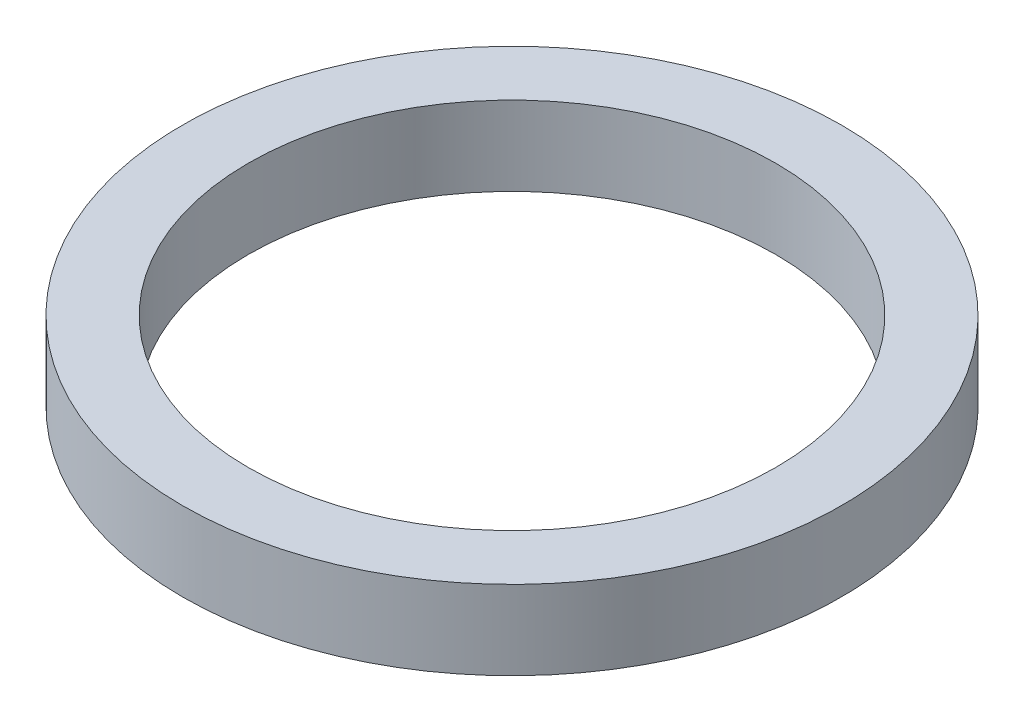
SolidWorks part; units mm, degrees
ref_plane "Front Plane" through (0, 0, 0) normal (0, 0, 1) x (1, 0, 0)
ref_plane "Top Plane" through (0, 0, 0) normal (0, 1, 0) x (1, 0, 0)
ref_plane "Right Plane" through (0, 0, 0) normal (1, 0, 0) x (0, 0, -1)
sketch "Sketch1" plane through (0, 0, 0) normal (0, 1, 0) x (1, 0, 0)
  circle A0 centre (0, 0) radius 37.5
  dimension "FLANGE_OD" = 75
extrude "Boss-Extrude1" add sketch "Sketch1" along normal blind 9
sketch "Sketch2" plane through (0, 0, 0) normal (0, 1, 0) x (1, 0, 0)
  circle A0 centre (0, 0) radius 30
  dimension "BORE_D" = 60
extrude "Cut-Extrude1" cut sketch "Sketch2" along normal through all
sketch "Sketch3" plane through (0, 9, 0) normal (0, 1, 0) x (1, 0, 0)
  circle A0 centre (0, 0) radius 16.5135 construction
  circle A1 centre (-16.5135, 0) radius 1.5
  dimension "BOLT_D" = 3
  dimension "BOLT_PCD" = 33.027
extrude "Cut-Extrude2" cut sketch "Sketch3" against normal blind 8.0433 rebuild error yes
pattern_circular "CirPattern1" count 6 over 360 rebuild error yes
